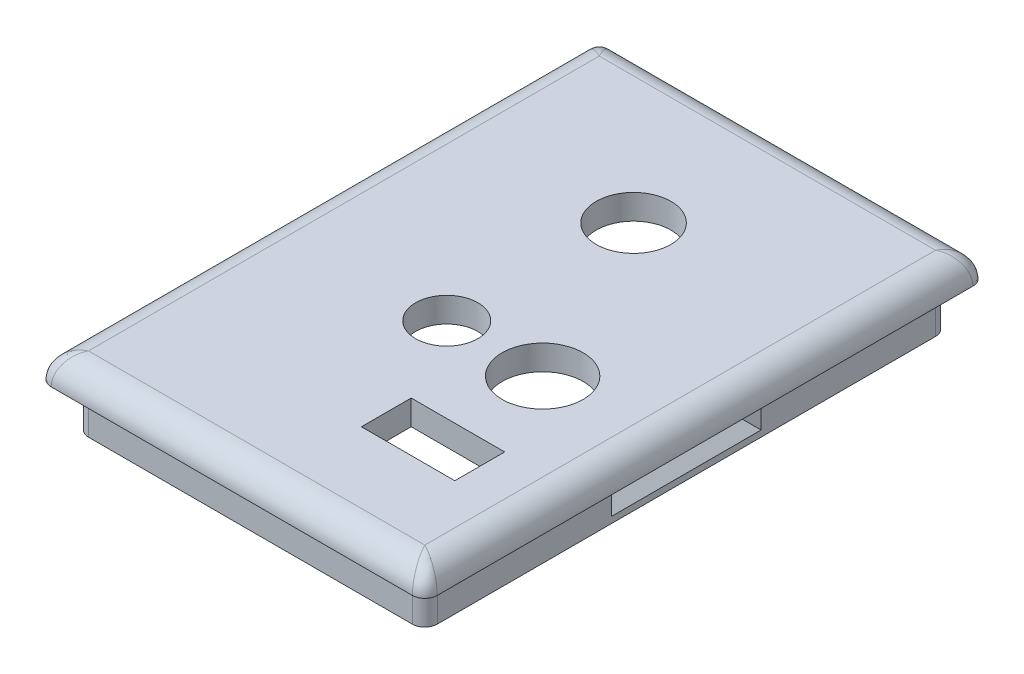
SolidWorks part; units mm, degrees
ref_plane "Front Plane" through (0, 0, 0) normal (0, 0, 1) x (1, 0, 0)
ref_plane "Top Plane" through (0, 0, 0) normal (0, 1, 0) x (1, 0, 0)
ref_plane "Right Plane" through (0, 0, 0) normal (1, 0, 0) x (0, 0, -1)
sketch "Sketch1" plane through (0, 0, 0) normal (0, 1, 0) x (1, 0, 0)
  line L1 (-15.5, -22.5) -> (15.5, -22.5)
  line L2 (-15.5, -22.5) -> (-15.5, 22.5)
  line L3 (-15.5, 22.5) -> (15.5, 22.5)
  line L4 (15.5, -22.5) -> (15.5, 22.5)
  line L5 (-15.5, -22.5) -> (15.5, 22.5) construction
  line L6 (-15.5, 22.5) -> (15.5, -22.5) construction
  point P0 (0, 0)
  dimension "D1" = 45
  dimension "D2" = 31
extrude "Boss-Extrude1" add sketch "Sketch1" along normal blind 2
sketch "Sketch2" plane through (0, 0, 0) normal (0, -1, 0) x (1, 0, 0)
  line L1 (-14, 21) -> (14, 21)
  line L2 (-14, 21) -> (-14, -21)
  line L3 (-14, -21) -> (14, -21)
  line L4 (14, 21) -> (14, -21)
  line L5 (-14, 21) -> (14, -21) construction
  line L6 (-14, -21) -> (14, 21) construction
  point P0 (0, 0)
  dimension "D1" = 42
  dimension "D2" = 28
extrude "Boss-Extrude2" add sketch "Sketch2" along normal blind 3.5
sketch "Sketch3" plane through (0, -3.5, 0) normal (0, -1, 0) x (1, 0, 0)
  line L1 (-12.5, 19.5) -> (12.5, 19.5)
  line L2 (-12.5, 19.5) -> (-12.5, -19.5)
  line L3 (-12.5, -19.5) -> (12.5, -19.5)
  line L4 (12.5, 19.5) -> (12.5, -19.5)
  line L5 (-12.5, 19.5) -> (12.5, -19.5) construction
  line L6 (-12.5, -19.5) -> (12.5, 19.5) construction
  point P0 (0, 0)
  dimension "D1" = 25
  dimension "D2" = 39
extrude "Cut-Extrude1" cut sketch "Sketch3" against normal blind 3.5
fillet "Fillet1" radius 2 4 edges at (0, 2, 22.5) (-15.5, 2, 0) (0, 2, -22.5) (15.5, 2, 0)
sketch "Sketch4" plane through (0, 2, 0) normal (0, 1, 0) x (1, 0, 0)
  line L0 (6.48, -12.82) -> (6.48, -4.02) construction
  line L1 (2.73, -10.82) -> (10.23, -10.82)
  line L2 (2.73, -10.82) -> (2.73, -14.82)
  line L3 (2.73, -14.82) -> (10.23, -14.82)
  line L4 (10.23, -10.82) -> (10.23, -14.82)
  line L5 (2.73, -10.82) -> (10.23, -14.82) construction
  line L6 (2.73, -14.82) -> (10.23, -10.82) construction
  line L7 (6.48, -4.02) -> (-1.22, -4.02) construction
  line L8 (6.48, -4.02) -> (6.48, 10.28) construction
  line L9 (6.48, 10.28) -> (-0.52, 10.28) construction
  line L10 (10.23, -14.82) -> (15.5, -14.82) construction
  line L12 (15.5, -22.5) -> (15.5, 22.5) construction
  line L14 (10.23, -14.82) -> (10.23, -22.5) construction
  line L15 (-15.5, -22.5) -> (15.5, -22.5) construction
  circle A0 centre (6.48, -4.02) radius 3.25
  circle A1 centre (-1.22, -4.02) radius 2.5
  circle A2 centre (-0.52, 10.28) radius 3
  point P4 (6.48, -12.82)
  dimension "D1" = 7.5
  dimension "D7" = 6
  dimension "D8" = 5
  dimension "D9" = 6.5
  dimension "D2" = 4
  dimension "D3" = 8.8
  dimension "D4" = 7.7
  dimension "D5" = 14.3
  dimension "D6" = 7
  dimension "D10" = 5.27
  dimension "D11" = 7.68
extrude "Cut-Extrude2" cut sketch "Sketch4" against normal blind 2
fillet "Fillet2" radius 1 4 edges at (14.9142, 1.4142, -21.9142) (-14.9142, 1.4142, -21.9142) (-14.9142, 1.4142, 21.9142) (14.9142, 1.4142, 21.9142)
sketch "Sketch5" plane through (14, 0, 0) normal (1, 0, 0) x (0, 0, -1)
  line L1 (-6, -1) -> (6, -1)
  line L2 (-6, -1) -> (-6, -3)
  line L3 (-6, -3) -> (6, -3)
  line L4 (6, -1) -> (6, -3)
  line L5 (-6, -1) -> (6, -3) construction
  line L6 (-6, -3) -> (6, -1) construction
  point P0 (0, -2)
  point P5 (0, 0)
  dimension "D1" = 2
  dimension "D2" = 12
extrude "Cut-Extrude3" cut sketch "Sketch5" against normal blind 1
chamfer "Chamfer1" distance 1 angle 45 4 edges at (13, -3, 0) (13, -2, 6) (13, -1, 0) (13, -2, -6)
sketch "Sketch6" plane through (-14, 0, 0) normal (-1, 0, 0) x (0, 0, 1)
  line L1 (-6, -1) -> (6, -1)
  line L2 (-6, -1) -> (-6, -3)
  line L3 (-6, -3) -> (6, -3)
  line L4 (6, -1) -> (6, -3)
  line L5 (-6, -1) -> (6, -3) construction
  line L6 (-6, -3) -> (6, -1) construction
  point P0 (0, -2)
  point P5 (0, 0)
  dimension "D1" = 2
  dimension "D2" = 12
extrude "Cut-Extrude4" cut sketch "Sketch6" against normal blind 1
chamfer "Chamfer2" distance 1 angle 45 4 edges at (-13, -2, -6) (-13, -3, 0) (-13, -2, 6) (-13, -1, 0)
fillet "Fillet3" radius 1 4 edges at (-14, -1.75, 21) (14, -1.75, 21) (-14, -1.75, -21) (14, -1.75, -21)
